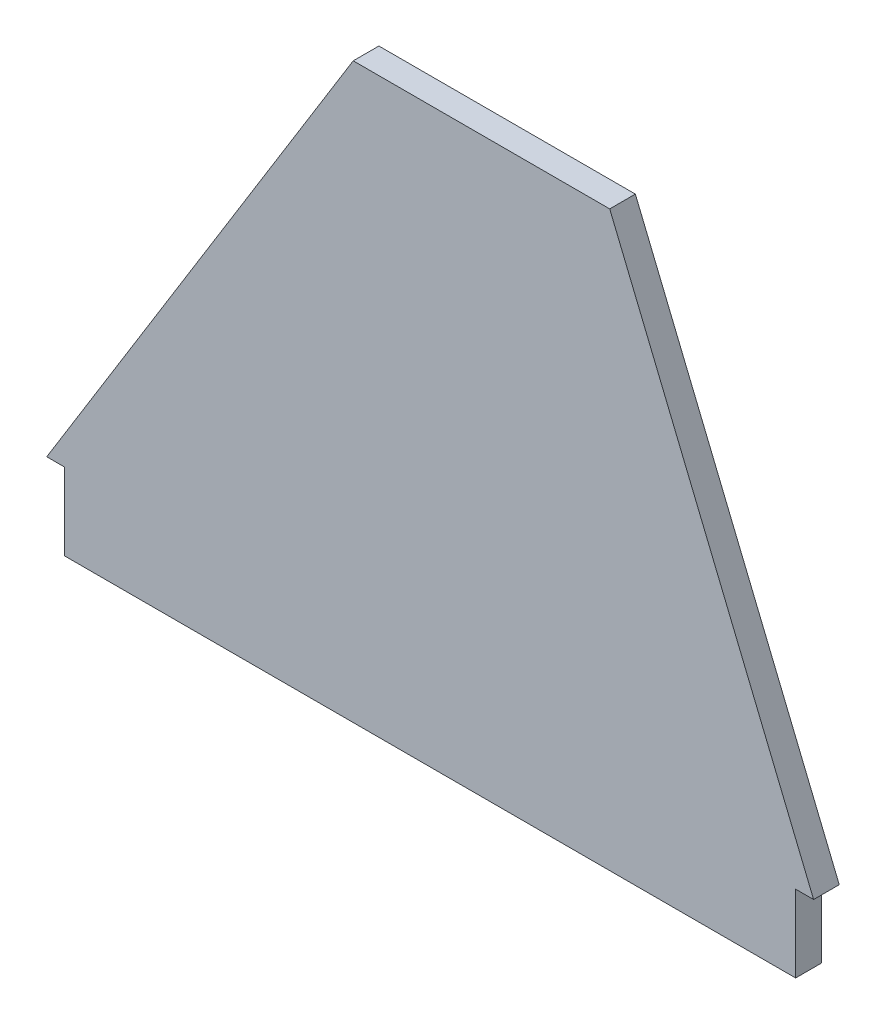
SolidWorks part; units mm, degrees
material "Balsa"
ref_plane "Front Plane" through (0, 0, 0) normal (0, 0, 1) x (1, 0, 0)
ref_plane "Top Plane" through (0, 0, 0) normal (0, 1, 0) x (1, 0, 0)
ref_plane "Right Plane" through (0, 0, 0) normal (1, 0, 0) x (0, 0, -1)
sketch "Sketch1" plane through (0, 0, 0) normal (0, 0, 1) x (1, 0, 0)
  line L0 (74.75, 15) -> (71.25, 15)
  line L1 (0, 111.7259) -> (35, 111.7259)
  line L5 (71.25, 15) -> (71.25, 0)
  line L6 (71.25, 0) -> (-71.25, 0)
  line L7 (-71.25, 0) -> (-71.25, 15)
  line L8 (-71.25, 15) -> (-74.75, 15)
  line L9 (0, 111.7259) -> (-15, 111.7259)
  line L10 (0, 0) -> (0, 111.7259) construction
  line L11 (-74.75, 15) -> (-15, 111.7259)
  line L12 (74.75, 15) -> (35, 111.7259)
  point P3 (0, 0)
  point P4 (0, 0)
  point P10 (0, 111.7259)
  dimension "D1" = 50
  dimension "D2" = 15
  dimension "D3" = 3.5
  dimension "D4" = 3.5
  dimension "D5" = 142.5
  dimension "D6" = 15
extrude "Boss-Extrude1" add sketch "Sketch1" along normal blind 5
